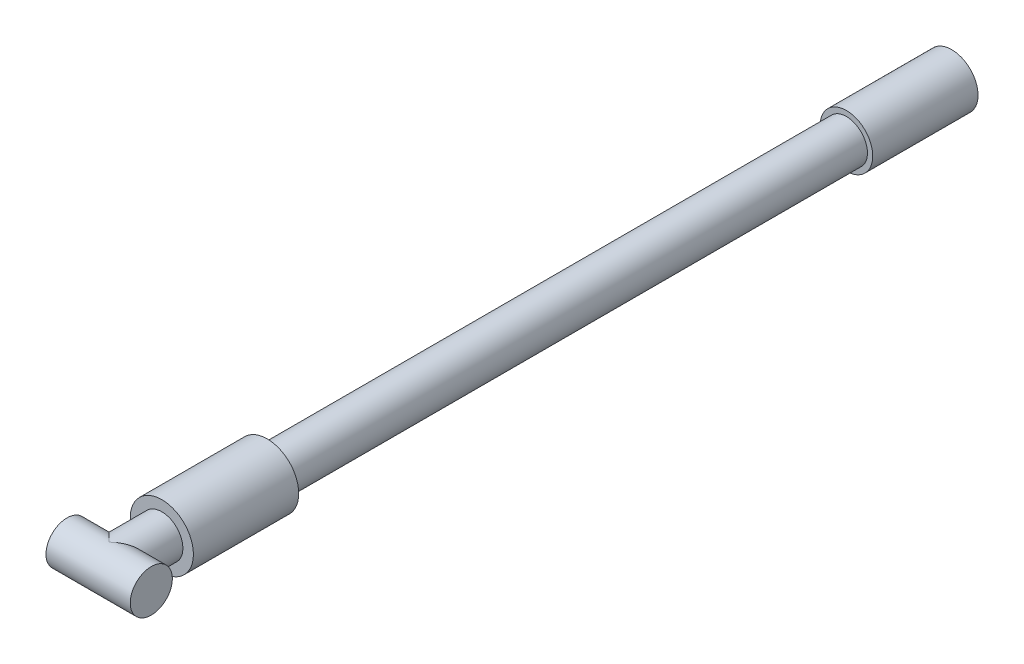
SolidWorks part; units mm, degrees
ref_plane "Front Plane" through (0, 0, 0) normal (0, 0, 1) x (1, 0, 0)
ref_plane "Top Plane" through (0, 0, 0) normal (0, 1, 0) x (1, 0, 0)
ref_plane "Right Plane" through (0, 0, 0) normal (1, 0, 0) x (0, 0, -1)
sketch "Sketch1" plane through (0, 0, 0) normal (0, 0, 1) x (1, 0, 0)
  circle A0 centre (0, 0) radius 4
  dimension "D1" = 8
extrude "Boss-Extrude1" add sketch "Sketch1" against normal blind 150
sketch "Sketch2" plane through (0, 0, -150) normal (0, 0, -1) x (-1, 0, 0)
  circle A0 centre (0, 0) radius 5
  dimension "D1" = 10
extrude "Boss-Extrude2" add sketch "Sketch2" against normal blind 20
sketch "Sketch3" plane through (0, 0, 0) normal (0, 0, 1) x (1, 0, 0)
  circle A0 centre (0, 0) radius 6
  dimension "D1" = 12
extrude "Boss-Extrude3" add sketch "Sketch3" against normal blind 20
sketch "Sketch4" plane through (0, 0, 0) normal (0, 0, 1) x (1, 0, 0)
  circle A0 centre (0, 0) radius 4
  dimension "D1" = 8
extrude "Boss-Extrude6" add sketch "Sketch4" along normal blind 10
sketch "Sketch6" plane through (0, 0, 0) normal (1, 0, 0) x (0, 0, -1)
  line L0 (-10, 4) -> (-10, -4) construction
  circle A0 centre (-10, 0) radius 4
extrude "Boss-Extrude7" add sketch "Sketch6" along normal blind 8 and the other way blind 8
sketch3d "3DSketch1"
  line L0 (0, -4, -20) -> (0, -4, -130) construction
  circle A0 centre (0, 0, -20) radius 4 construction
  circle A1 centre (0, 0, -130) radius 4 construction
  point P4 (0, 0, -24)
  point P7 (0, 0, -126)
